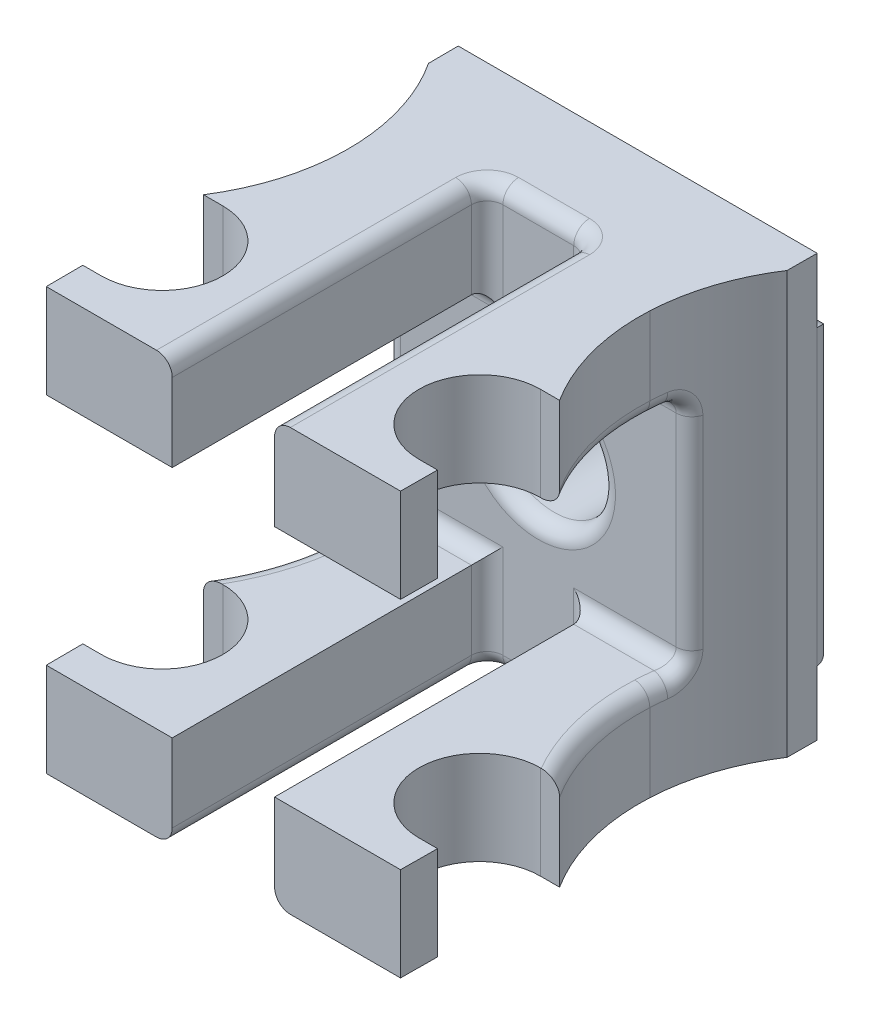
SolidWorks part; units mm, degrees
ref_plane "Front Plane" through (0, 0, 0) normal (1, 0, 0) x (0, 1, 0)
ref_plane "Top Plane" through (0, 0, 0) normal (0, 0, 1) x (0, 1, 0)
ref_plane "Right Plane" through (0, 0, 0) normal (0, 1, 0) x (-1, 0, 0)
sketch "Sketch2" plane through (0, 0, 0) normal (0, 0, 1) x (0, 1, 0)
  line L1 (-23.622, 28.956) -> (23.622, 28.956)
  line L2 (-23.622, 28.956) -> (-23.622, -28.956)
  line L3 (-23.622, -28.956) -> (23.622, -28.956)
  line L4 (23.622, 28.956) -> (23.622, -28.956)
  line L5 (-23.622, 28.956) -> (23.622, -28.956) construction
  line L6 (-23.622, -28.956) -> (23.622, 28.956) construction
  point P0 (0, 0)
  dimension "D1" = 47.244
  dimension "D2" = 57.912
extrude "Boss-Extrude1" add sketch "Sketch2" along normal blind 2.54
sketch "Sketch3" plane through (0, 0, 2.54) normal (0, 0, 1) x (1, 0, 0)
  circle A0 centre (0, 0) radius 9.779
  dimension "D1" = 19.558
extrude "Cut-Extrude1" cut sketch "Sketch3" against normal mid plane 157.48
sketch "Sketch5" plane through (0, 0, 0) normal (0, 1, 0) x (-1, 0, 0)
  line L0 (0, 0) -> (0, 69.3762) construction
  line L1 (-28.956, 2.54) -> (28.956, 2.54)
  line L2 (0, 34.6881) -> (-15.6223, 24.9262) construction
  line L5 (9.779, 2.54) -> (-9.779, 2.54) construction
  line L8 (28.956, 2.54) -> (28.575, 69.3762)
  line L9 (-28.575, 69.3762) -> (28.575, 69.3762)
  line L10 (-28.956, 2.54) -> (-28.575, 69.3762)
  line L11 (0, 34.6881) -> (15.6223, 24.9262) construction
  circle A0 centre (15.6223, 24.9262) radius 44.45 construction
  circle A1 centre (-15.6223, 24.9262) radius 44.45 construction
  point P6 (0, 2.54)
  point P13 (0, 69.3762)
  dimension "D3" = 88.9
  dimension "D1" = 57.15
  dimension "D2" = 58
extrude "Boss-Extrude2" add sketch "Sketch5" along normal mid plane 68.0212
sketch "Sketch6" plane through (0, 23.622, 0) normal (0, 1, 0) x (-1, 0, 0)
  line L0 (0, 0) -> (0, 69.3762) construction
  line L2 (-8.255, 69.3762) -> (8.255, 69.3762)
  line L3 (-8.255, 69.3762) -> (-8.255, 18.5762)
  line L5 (8.255, 69.3762) -> (8.255, 18.5762)
  line L6 (-28.575, 69.3762) -> (28.575, 69.3762) construction
  line L7 (-8.255, 18.5762) -> (8.255, 18.5762)
  point P4 (0, 34.6881)
  point P17 (0, 18.5762)
  dimension "D1" = 16.51
  dimension "D2" = 50.8
extrude "Cut-Extrude2" cut sketch "Sketch6" against normal through all both and the other way through all
sketch "Sketch7" plane through (0, 23.622, 0) normal (0, 1, 0) x (-1, 0, 0)
  line L2 (0, 0) -> (0, 34.3406) construction
  line L3 (28.956, 2.54) -> (28.956, 0) construction
  line L6 (-28.956, 0) -> (28.956, 0) construction
  line L7 (12.631, 17.1842) -> (0, 17.1703) construction
  line L8 (-28.2599, 63.4449) -> (-12.631, 17.1842) construction
  line L9 (0, 17.1703) -> (-12.631, 17.1842) construction
  line L10 (-12.631, 17.1842) -> (-28.2599, 63.4449) construction
  line L11 (0, 25.9842) -> (0, -25.9842) construction
  line L12 (28.2599, 63.4449) -> (12.631, 17.1842) construction
  line L14 (-28.956, 2.54) -> (-28.575, 69.3762) construction
  line L16 (15.8234, 53.6544) -> (35.4044, 53.6544) construction
  line L19 (25.6139, 43.8638) -> (38.3139, 43.8638)
  line L24 (-28.6758, 51.6993) -> (-8.255, 51.6993) construction
  line L25 (-8.255, 69.3762) -> (-8.255, 18.5762) construction
  line L26 (-8.255, 51.6993) -> (-8.255, 64.3776) construction
  line L27 (-8.255, 64.3776) -> (-28.6758, 51.6993) construction
  line L28 (-25.6139, 63.4449) -> (-38.3139, 63.4449)
  line L29 (-38.3139, 63.4449) -> (-35.3485, 54.6991)
  line L30 (-15.8234, 53.6544) -> (-35.4044, 53.6544) construction
  line L31 (-38.3139, 43.8638) -> (-35.3485, 52.6096)
  line L32 (-25.6139, 43.8638) -> (-38.3139, 43.8638)
  line L33 (38.3139, 43.8638) -> (35.3485, 52.6096)
  line L34 (38.3139, 63.4449) -> (35.3485, 54.6991)
  line L35 (25.6139, 63.4449) -> (38.3139, 63.4449)
  arc A10 (-25.6139, 43.8638) -> (-25.6139, 63.4449) centre (-25.6139, 53.6544) ccw
  arc A11 (-35.3485, 54.6991) -> (-35.3485, 52.6096) centre (-25.6139, 53.6544) ccw
  arc A12 (35.3485, 54.6991) -> (35.3485, 52.6096) centre (25.6139, 53.6544) cw
  arc A13 (25.6139, 43.8638) -> (25.6139, 63.4449) centre (25.6139, 53.6544) cw
  dimension "D1" = 12.7
  dimension "D2" = 9.7905
  dimension "D3" = 6.3925
  dimension "D4" = 9.3579
  dimension "D5" = 2.54
  dimension "D6" = 17.1842
  dimension "D7" = 51.6993
  dimension "D8" = 52.6096
  dimension "D9" = 53.6544
extrude "Cut-Extrude4" cut sketch "Sketch7" against normal through all both and the other way through all
sketch "Sketch8" plane through (0, 23.622, 0) normal (0, 1, 0) x (-1, 0, 0)
  line L0 (0, 0) -> (0, 69.3762) construction
  line L1 (-28.7204, 43.8638) -> (-31.2982, 9.1623) construction
  line L2 (-8.255, 18.5762) -> (8.255, 18.5762) construction
  line L3 (-31.2982, 9.1623) -> (-31.5578, 3.8539)
  line L4 (-38.735, 24.0873) -> (-8.255, 24.0873) construction
  line L7 (-8.255, 69.3762) -> (-8.255, 18.5762) construction
  line L10 (-28.7204, 43.8638) -> (-31.2982, 9.1623)
  line L12 (31.5578, 3.8539) -> (28.956, 2.54) construction
  line L15 (38.735, 24.0873) -> (8.255, 24.0873) construction
  line L19 (-31.5578, 3.8539) -> (-28.956, 2.54) construction
  line L20 (28.7204, 43.8638) -> (31.2982, 9.1623) construction
  line L21 (28.7204, 43.8638) -> (31.2982, 9.1623)
  line L22 (31.2982, 9.1623) -> (31.5578, 3.8539)
  arc A5 (-23.495, 24.0873) -> (-31.5578, 3.8539) centre (-57.0989, 25.755) cw
  arc A6 (-23.495, 24.0873) -> (-28.7204, 43.8638) centre (-57.2008, 25.76) ccw
  arc A7 (23.495, 24.0873) -> (28.7204, 43.8638) centre (57.2008, 25.76) cw
  arc A8 (23.495, 24.0873) -> (31.5578, 3.8539) centre (57.0989, 25.755) ccw
  point P26 (-27.1103, 46.2999)
  point P27 (-28.7223, 43.5339)
  point P28 (0, 0)
  point P29 (-29.8855, 24.1239)
  point P30 (-29.8855, 1.5259)
  point P31 (-28.7223, 25.3119)
  point P32 (-35.3679, 24.0873)
  point P33 (-28.956, 43.5339)
  dimension "D1" = 15.24
extrude "Cut-Extrude9" cut sketch "Sketch8" against normal through all both and the other way through all
sketch "Sketch9" plane through (0, 0, 0) normal (1, 0, 0) x (0, 1, 0)
  line L0 (0, 0) -> (0, 69.3762) construction
  line L6 (-18.883, 18.5762) -> (18.883, 18.5762)
  line L8 (-18.883, 18.5762) -> (-18.883, 69.3762)
  line L9 (-18.883, 69.3762) -> (18.883, 69.3762)
  line L10 (18.883, 18.5762) -> (18.883, 69.3762)
  line L11 (-34.0106, 18.5762) -> (34.0106, 18.5762) construction
  point P4 (0, 34.6881)
  point P5 (0, 34.6881)
extrude "Cut-Extrude7" cut sketch "Sketch9" against normal mid plane 83.2612
ref_plane "Plane1" through (-38.9694, 0, 0.2221) normal (-1, 0, 0.0057) x (0.0057, 0, 1)
ref_plane "Plane2" through (0, 33.622, 0) normal (0, 1, 0) x (1, 0, 0)
sketch "Sketch10" plane through (0, 0, 0) normal (0, 0, -1) x (1, 0, 0)
  circle A0 centre (0, 0) radius 9.906
  dimension "D1" = 19.812
extrude "Cut-Extrude10" cut sketch "Sketch10" against normal blind 60.4012
sketch "Sketch11" plane through (0, 0, 0) normal (0, 0, -1) x (1, 0, 0)
  line L0 (0, 0) -> (0, 23.622) construction
  line L1 (-28.956, 23.622) -> (28.956, 23.622) construction
  line L2 (0, 23.622) -> (-26.4035, 23.622) construction
  line L3 (-28.956, -23.622) -> (-28.956, 23.622) construction
  line L4 (-28.956, 23.622) -> (-28.956, -23.622)
  line L5 (-28.956, -23.622) -> (-26.4035, -23.622)
  line L6 (28.956, -23.622) -> (-28.956, -23.622) construction
  line L7 (-26.4035, -23.622) -> (-26.4035, 23.622)
  line L8 (-26.4035, 23.622) -> (-28.956, 23.622)
  line L9 (26.4035, 23.622) -> (28.956, 23.622)
  line L10 (26.4035, -23.622) -> (26.4035, 23.622)
  line L11 (28.956, -23.622) -> (26.4035, -23.622)
  line L12 (28.956, 23.622) -> (28.956, -23.622)
  dimension "D1" = 2.5525
fillet "Fillet16" radius 2.54 30 edges at (-24.5732, -18.883, 34.381) (-24.5732, 18.883, 34.381) (24.5732, 18.883, 34.381) (24.5732, -18.883, 34.381) (8.255, -34.0106, 43.9762) (-8.255, -34.0106, 43.9762) (-23.7477, -18.883, 21.3166) (-23.7477, 18.883, 21.3166) (-8.255, 34.0106, 43.9762) (8.255, 34.0106, 43.9762) (23.7477, 18.883, 21.3166) (23.7477, -18.883, 21.3166) (-28.956, 0, 0) (0, -23.622, 0) (28.956, 0, 0) (0, 23.622, 0) (-9.906, 0, 0) (0, -34.0106, 18.5762) (-8.255, -26.4468, 18.5762) (-16.2417, -18.883, 18.5762) (-24.2284, 0, 18.5762) (-16.2417, 18.883, 18.5762) (-8.255, 26.4468, 18.5762) (0, 34.0106, 18.5762) (8.255, 26.4468, 18.5762) (16.2417, 18.883, 18.5762) (24.2284, 0, 18.5762) (16.2417, -18.883, 18.5762) (8.255, -26.4468, 18.5762) (-9.906, 0, 18.5762)
sketch "Sketch12" plane through (0, 0, 0) normal (0, 0, -1) x (1, 0, 0)
  line L0 (-28.956, 0) -> (28.956, 0) construction
  line L3 (28.956, 23.622) -> (28.956, -23.622) construction
  line L4 (-28.956, 23.622) -> (-28.956, 21.082)
  line L5 (-28.956, 23.622) -> (-28.956, -23.622) construction
  line L6 (-28.956, 21.082) -> (28.956, 21.082)
  line L7 (28.956, 21.082) -> (28.956, 23.622)
  line L8 (28.956, 23.622) -> (-28.956, 23.622)
  line L9 (28.956, -23.622) -> (-28.956, -23.622)
  line L10 (28.956, -21.082) -> (28.956, -23.622)
  line L11 (-28.956, -21.082) -> (28.956, -21.082)
  line L12 (-28.956, -23.622) -> (-28.956, -21.082)
  point P5 (0, 0)
  dimension "D1" = 2.54
extrude "Boss-Extrude3" [suppressed] add sketch "Sketch12" along normal blind 1.8161
sketch "Sketch13" [suppressed] plane through (23.5649, 0, 0) normal (1, 0, 0) x (0, 1, 0)
  line L0 (0, 0) -> (-26.3906, 0) construction
  line L1 (28.9306, 0) -> (-28.9306, 0) construction
  line L2 (-28.9306, 2.54) -> (-28.9306, -1.8161) construction
  line L3 (-28.9306, 0) -> (-28.9306, -1.8161) construction
  line L4 (-27.6606, -1.016) -> (-27.6606, -1.3081)
  line L5 (-26.3906, -1.8161) -> (-26.3906, 0)
  line L6 (0, 0) -> (0, -6.0893) construction
  line L7 (0, -24.5224) -> (0, 64.3776) construction
  line L8 (-26.3906, -1.8161) -> (-28.1686, -1.8161)
  line L9 (-27.6606, -1.016) -> (-28.4226, -1.016)
  line L10 (-28.4226, -1.016) -> (-28.4226, 0)
  line L11 (-28.4226, 0) -> (-28.9306, 0) construction
  line L12 (-26.3906, 0) -> (-28.4226, 0)
  line L13 (28.4226, 0) -> (28.9306, 0) construction
  line L14 (28.9306, 0) -> (28.9306, -1.8161) construction
  line L15 (26.3906, 0) -> (28.4226, 0)
  line L16 (28.4226, -1.016) -> (28.4226, 0)
  line L17 (27.6606, -1.016) -> (28.4226, -1.016)
  line L18 (26.3906, -1.8161) -> (28.1686, -1.8161)
  line L19 (26.3906, -1.8161) -> (26.3906, 0)
  line L20 (27.6606, -1.016) -> (27.6606, -1.3081)
  arc A0 (-27.6606, -1.3081) -> (-28.1686, -1.8161) centre (-28.1686, -1.3081) cw
  arc A1 (27.6606, -1.3081) -> (28.1686, -1.8161) centre (28.1686, -1.3081) ccw
  dimension "D3" = 0.508
  dimension "D1" = 1.016
  dimension "D2" = 0.762
  dimension "D4" = 0.2921
extrude "Cut-Extrude11" [suppressed] cut sketch "Sketch13" against normal through all
fillet "Fillet15" [suppressed] radius 0.254
